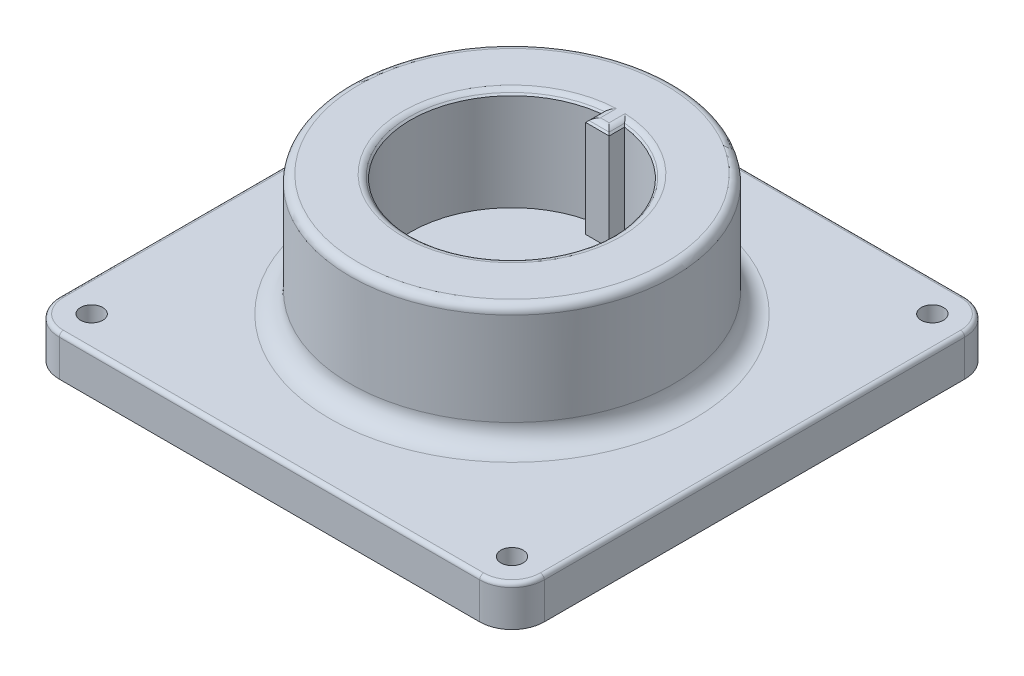
SolidWorks part; units mm, degrees
ref_plane "Front Plane" through (0, 0, 0) normal (0, 0, 1) x (1, 0, 0)
ref_plane "Top Plane" through (0, 0, 0) normal (0, 1, 0) x (1, 0, 0)
ref_plane "Right Plane" through (0, 0, 0) normal (1, 0, 0) x (0, 0, -1)
sketch "Sketch1" plane through (0, 0, 0) normal (0, 1, 0) x (1, 0, 0)
  line L0 (0, 59.5258) -> (0, -57.6138) construction
  line L1 (-78.936, 0) -> (74.7859, 0) construction
  line L3 (-60, -60) -> (60, -60)
  line L4 (-60, -60) -> (-60, 60)
  line L5 (-60, 60) -> (60, 60)
  line L6 (60, -60) -> (60, 60)
  line L7 (-60, -60) -> (60, 60) construction
  line L8 (-60, 60) -> (60, -60) construction
  point P5 (0, 0)
  dimension "D1" = 120
  dimension "D2" = 120
extrude "Boss-Extrude1" add sketch "Sketch1" along normal blind 10
ref_axis "Axis1" through (0, 0, 0) along (0, 1, 0)
sketch "Sketch2" plane through (0, 10, 0) normal (0, 1, 0) x (1, 0, 0)
  line L0 (-60, 60) -> (60, -60) construction
  line L1 (-60, 60) -> (-60, -60) construction
  circle A0 centre (-52, 52) radius 2.75
  dimension "D1" = 5.5
  dimension "D2" = 8
extrude "Cut-Extrude1" cut sketch "Sketch2" against normal through all
pattern_circular "CirPattern1" count 4 over 360 about axis through (0, 0, 0) along (0, 1, 0) of "Cut-Extrude1"
fillet "Fillet1" radius 8 4 edges at (-60, 5, 60) (60, 5, 60) (60, 5, -60) (-60, 5, -60)
fillet "Fillet2" radius 1 8 edges at (-57.6569, 10, -57.6569) (0, 10, -60) (57.6569, 10, -57.6569) (60, 10, 0) (57.6569, 10, 57.6569) (0, 10, 60) (-57.6569, 10, 57.6569) (-60, 10, 0)
sketch "Sketch3" plane through (0, 10, 0) normal (0, 1, 0) x (1, 0, 0)
  circle A0 centre (0, 0) radius 40
  dimension "D1" = 80
extrude "Boss-Extrude2" add sketch "Sketch3" along normal blind 30
sketch "Sketch4" plane through (0, 40, 0) normal (0, 1, 0) x (1, 0, 0)
  circle A0 centre (0, 0) radius 25.1
  dimension "D1" = 50.2
extrude "Cut-Extrude2" cut sketch "Sketch4" against normal blind 25
sketch "Sketch5" plane through (0, 40, 0) normal (0, 1, 0) x (1, 0, 0)
  line L0 (0, 0) -> (0, 32.3516) construction
  line L1 (2.9, 21.1319) -> (-2.9, 21.1319)
  line L2 (-2.9, 21.1319) -> (-2.9, 24.9319)
  line L3 (2.9, 21.1319) -> (2.9, 24.9319)
  circle A0 centre (0, 0) radius 25.1 construction
  circle A1 centre (0, 0) radius 25.1 construction
  arc A2 (2.9, 24.9319) -> (-2.9, 24.9319) centre (0, 0) ccw
  point P9 (0, 21.1319)
  dimension "D1" = 5.8
  dimension "D2" = 3.8
extrude "Boss-Extrude3" add sketch "Sketch5" against normal up to next
chamfer "Chamfer1" distance 1 angle 45 4 edges at (-2.9, 40, -23.0319) (0, 40, -21.1319) (2.9, 40, -23.0319) (0, 40, 25.1)
fillet "Fillet3" radius 2 5 edges at (0, 40, 40) (1.9, 40, -24.0813) (0, 40, -22.1319) (-1.9, 40, -24.0813) (0, 40, 26.1)
fillet "Fillet4" radius 5 1 edges at (0, 10, -40)
